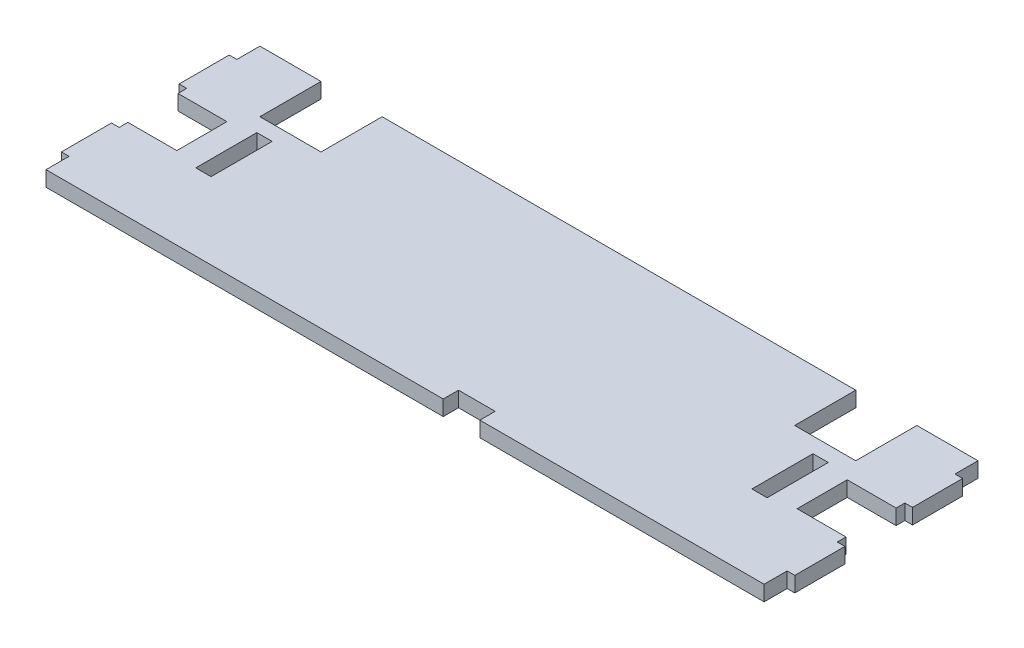
SolidWorks part; units mm, degrees
ref_plane "Front Plane" through (0, 0, 0) normal (0, 0, 1) x (1, 0, 0)
ref_plane "Top Plane" through (0, 0, 0) normal (0, 1, 0) x (1, 0, 0)
ref_plane "Right Plane" through (0, 0, 0) normal (1, 0, 0) x (0, 0, -1)
sketch "Sketch1" plane through (0, 0, 0) normal (0, 1, 0) x (1, 0, 0)
  line L0 (0, 72.39) -> (0, -44.45) construction
  line L1 (149.225, -44.45) -> (31.115, -44.45)
  line L2 (149.225, -44.45) -> (149.225, -34.8747)
  line L3 (149.225, 44.45) -> (123.825, 44.45)
  line L4 (-149.225, -44.45) -> (-149.225, -34.8747)
  line L5 (149.225, -44.45) -> (-149.225, 44.45) construction
  line L6 (149.225, 44.45) -> (-149.225, -44.45) construction
  line L7 (149.225, 10.414) -> (128.905, 10.414)
  line L9 (149.225, -10.414) -> (128.905, -10.414)
  line L10 (128.905, 10.414) -> (128.905, -10.414)
  line L11 (-123.825, 44.45) -> (-149.225, 44.45)
  line L13 (-149.225, -10.414) -> (-128.905, -10.414)
  line L14 (-128.905, 10.414) -> (-128.905, -10.414)
  line L15 (-149.225, 10.414) -> (-128.905, 10.414)
  line L17 (-127, 0) -> (127, 0) construction
  line L18 (-149.225, 14.0467) -> (-152.4, 14.0467)
  line L20 (-149.225, 34.8747) -> (-152.4, 34.8747)
  line L21 (-152.4, 14.0467) -> (-152.4, 34.8747)
  line L22 (-149.225, -34.8747) -> (-152.4, -34.8747)
  line L23 (-152.4, -14.0467) -> (-152.4, -34.8747)
  line L24 (-149.225, -14.0467) -> (-152.4, -14.0467)
  line L27 (149.225, -14.0467) -> (152.4, -14.0467)
  line L28 (152.4, -14.0467) -> (152.4, -34.8747)
  line L29 (149.225, -34.8747) -> (152.4, -34.8747)
  line L30 (149.225, 34.8747) -> (152.4, 34.8747)
  line L31 (152.4, 14.0467) -> (152.4, 34.8747)
  line L32 (149.225, 14.0467) -> (152.4, 14.0467)
  line L34 (-149.225, 34.8747) -> (-149.225, 44.45)
  line L35 (-149.225, -14.0467) -> (-149.225, -10.414)
  line L36 (149.225, 34.8747) -> (149.225, 44.45)
  line L37 (149.225, -14.0467) -> (149.225, -10.414)
  line L38 (-149.225, 10.414) -> (-149.225, 14.0467)
  line L39 (149.225, 10.414) -> (149.225, 14.0467)
  line L40 (-123.825, 44.45) -> (-123.825, 19.05)
  line L41 (-123.825, 19.05) -> (-98.425, 19.05)
  line L42 (-98.425, 44.45) -> (-98.425, 19.05)
  line L44 (98.425, 44.45) -> (98.425, 19.05)
  line L45 (98.425, 19.05) -> (123.825, 19.05)
  line L46 (123.825, 44.45) -> (123.825, 19.05)
  line L47 (98.425, 44.45) -> (-98.425, 44.45)
  line L48 (15.875, -44.45) -> (-149.225, -44.45)
  line L50 (15.875, -44.45) -> (15.875, -38.1)
  line L51 (15.875, -38.1) -> (31.115, -38.1)
  line L52 (31.115, -44.45) -> (31.115, -38.1)
  point P0 (0, 0)
  point P6 (127, 0)
  dimension "D1" = 298.45
  dimension "D2" = 88.9
  dimension "D3" = 20.828
  dimension "D5" = 3.175
  dimension "D6" = 20.828
  dimension "D4" = 20.32
  dimension "D7" = 25.4
  dimension "D8" = 25.4
  dimension "D9" = 25.4
  dimension "D10" = 25.4
  dimension "D12" = 25.4
  dimension "D11" = 25.4
  dimension "D13" = 304.8
  dimension "D14" = 15.24
  dimension "D15" = 6.35
  dimension "D16" = 165.1
extrude "Boss-Extrude1" add sketch "Sketch1" along normal mid plane 6.35
sketch "Sketch2" plane through (0, 0, 0) normal (0, 1, 0) x (1, 0, 0)
  line L1 (112.395, -12.7) -> (118.745, -12.7)
  line L2 (112.395, -12.7) -> (112.395, 12.7)
  line L3 (112.395, 12.7) -> (118.745, 12.7)
  line L4 (118.745, -12.7) -> (118.745, 12.7)
  line L5 (112.395, -12.7) -> (118.745, 12.7) construction
  line L6 (112.395, 12.7) -> (118.745, -12.7) construction
  line L13 (128.905, -10.414) -> (128.905, 10.414) construction
  line L15 (-112.395, -12.7) -> (-112.395, 12.7)
  line L16 (-112.395, -12.7) -> (-118.745, -12.7)
  line L17 (-118.745, -12.7) -> (-118.745, 12.7)
  line L18 (-112.395, 12.7) -> (-118.745, 12.7)
  point P0 (115.57, 0)
  point P10 (128.905, 0)
  dimension "D2" = 10.16
  dimension "D4" = 25.4
  dimension "D5" = 6.35
extrude "Cut-Extrude1" cut sketch "Sketch2" against normal through all both and the other way through all
equation "\"length\"= \"Avionics_Board_Length\""
equation "\"width\"=3.5"
equation "\"height\"= 0.25"
equation "\"D2@Sketch1\"=\"width\""
equation "\"eyebolt width\"= 0.82"
equation "\"eyebolt length\"= 0.8"
equation "\"D3@Sketch1\"=\"eyebolt width\""
equation "\"D4@Sketch1\"=\"eyebolt length\""
equation "\"lead screw holder height\"= 2.76"
equation "\"distance from holders to board\"=0.4"
equation "\"Mid_Coupler_Length\" = 12in"
equation "\"Avionics_Bulkhead_Thickness\" = 0.25in"
equation "\"Avionics_Bulkhead_Lip\" = 0.125in"
equation "\"Avionics_Board_Length\" = \"Mid_Coupler_Length\" - 2*\"Avionics_Bulkhead_Lip\""
equation "\"Body_Tube_OD\"= 4.024in"
equation "\"D1@Sketch1\"=\"length\""
